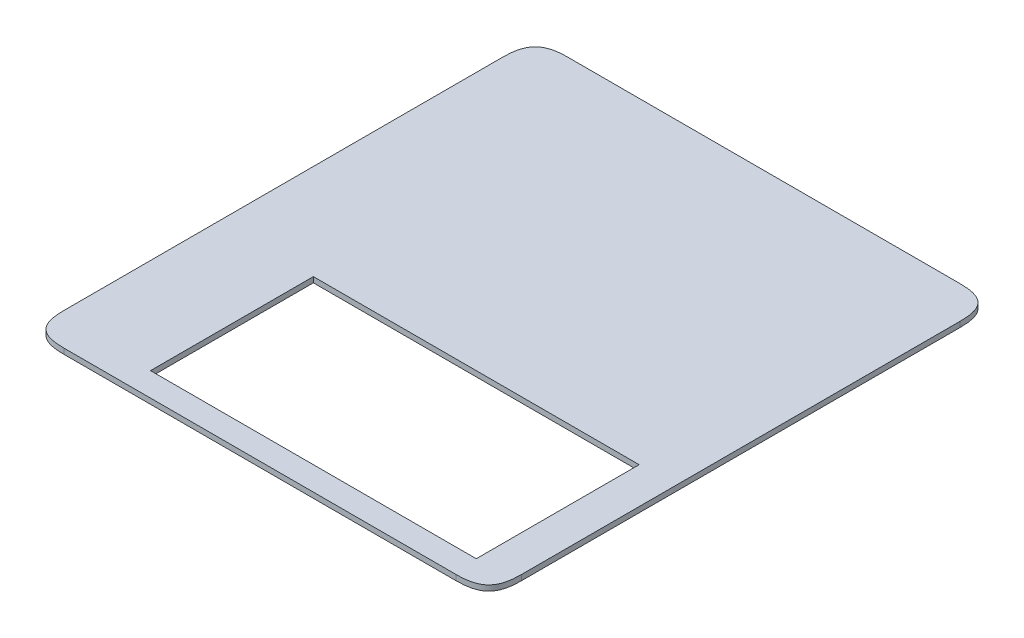
SolidWorks part; units mm, degrees
ref_plane "Front Plane" through (0, 0, 0) normal (0, 0, 1) x (1, 0, 0)
ref_plane "Top Plane" through (0, 0, 0) normal (0, 1, 0) x (1, 0, 0)
ref_plane "Right Plane" through (0, 0, 0) normal (1, 0, 0) x (0, 0, -1)
sketch "Sketch1" plane through (0, 0, 0) normal (0, 1, 0) x (1, 0, 0)
  line L1 (0, 0) -> (337, 0)
  line L2 (0, 0) -> (0, 371.22)
  line L3 (0, 371.22) -> (337, 371.22)
  line L4 (337, 0) -> (337, 371.22)
  line L5 (70.28, 137.5) -> (310.28, 137.5)
  line L6 (70.28, 137.5) -> (70.28, 17.5)
  line L7 (70.28, 17.5) -> (310.28, 17.5)
  line L8 (310.28, 137.5) -> (310.28, 17.5)
  dimension "D1" = 337
  dimension "D2" = 371.22
  dimension "D3" = 240
  dimension "D4" = 120
  dimension "D5" = 17.5
  dimension "D6" = 26.72
extrude "Boss-Extrude1" add sketch "Sketch1" against normal blind 4
fillet "Fillet1" radius 24 4 edges at (0, -2, 0) (337, -2, 0) (0, -2, -371.22) (337, -2, -371.22) conic rho 0.55
